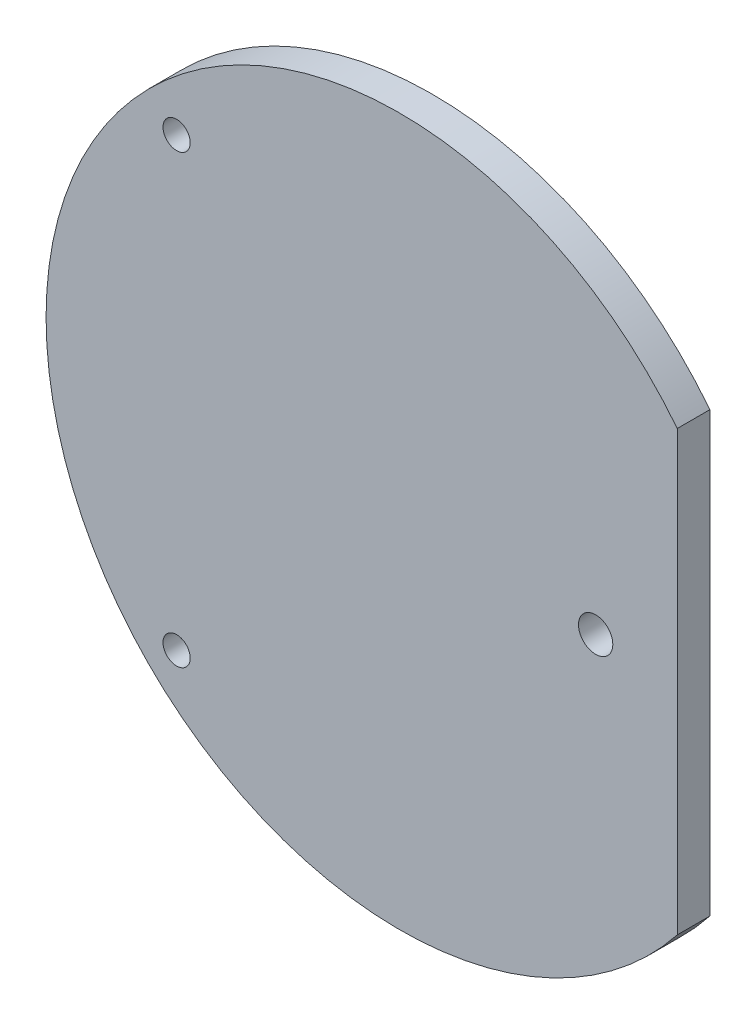
SolidWorks part; units mm, degrees
ref_plane "Спереди" through (0, 0, 0) normal (0, 0, 1) x (1, 0, 0)
ref_plane "Сверху" through (0, 0, 0) normal (0, 1, 0) x (1, 0, 0)
ref_plane "Справа" through (0, 0, 0) normal (1, 0, 0) x (0, 0, -1)
sketch "Эскиз1" plane through (0, 0, 0) normal (0, 0, 1) x (1, 0, 0)
  circle A0 centre (0, 0) radius 32.5
  dimension "D1" = 65
extrude "Бобышка-Вытянуть1" add sketch "Эскиз1" along normal blind 3
hole_wizard "Сверление под метчик M3x0.51" positions "Эскиз4" profile "Эскиз3" hole size "M3x0.5" standard "Ansi Metric"
sketch "Эскиз4" plane through (0, 0, 3) normal (0, 0, 1) x (1, 0, 0)
  line L1 (-36.4359, 0) -> (51.5308, 0) construction
  line L3 (0, 0) -> (-33.1888, 33.1888) construction
  circle A0 centre (0, 0) radius 29 construction
  circle A2 centre (-20.5061, 20.5061) radius 1.575
  circle A3 centre (-20.5061, -20.5061) radius 1.575
  point P31 (-20.5061, 20.5061)
  dimension "D1" = 58
  dimension "D2" = 3.15
  dimension "D3" = 45
sketch "Эскиз3" plane through (-20.5061, 20.5061, 3) normal (1, 0, 0) x (0, -1, 0)
  line L0 (0, 0) -> (0, 7.7511)
  line L1 (0, 7.7511) -> (1.25, 7)
  line L2 (1.25, 7) -> (1.25, 0)
  line L5 (1.25, 0) -> (0, 0)
  line L10 (0, 7.7511) -> (-1.25, 7) construction
  line L11 (0, -6.35) -> (0, 107.95) construction
  dimension "Диаметр отверстия" = 2.5
  dimension "Глубина отверстия" = 7
  dimension "Угол заточки сверла" = 118
pattern_circular "Круговой массив4" count 2 every 90 about axis through (0, 0, 3) along (0, 0, -1) of "Сверление под метчик M3x0.51" reverse direction yes
sketch "Эскиз5" plane through (0, 0, 0) normal (0, 0, -1) x (-1, 0, 0)
  line L0 (-25.5, -20.1494) -> (-25.5, 20.1494)
  arc A0 (-25.5, 20.1494) -> (-25.5, -20.1494) centre (0, 0) ccw
  point P5 (0, 0)
extrude "Вырез-Вытянуть2" cut sketch "Эскиз5" against normal blind 10
hole_wizard "Сверло под метчик  спиральное M31" positions "Эскиз6" profile "Эскиз7" hole size "M3x0.5" standard "Ansi Metric"
sketch "Эскиз6" plane through (0, 0, 3) normal (0, 0, 1) x (1, 0, 0)
  point P0 (18, 0)
  point P3 (14.9055, 0)
  dimension "D1" = 18
sketch "Эскиз7" plane through (18, 0, 3) normal (1, 0, 0) x (0, -1, 0)
  line L0 (0, 0) -> (0, 7.9464)
  line L1 (0, 7.9464) -> (1.575, 7)
  line L2 (1.575, 7) -> (1.575, 0)
  line L5 (1.575, 0) -> (0, 0)
  line L10 (0, 7.9464) -> (-1.575, 7) construction
  line L11 (0, -6.35) -> (0, 107.95) construction
  dimension "Диаметр отверстия" = 3.15
  dimension "Глубина отверстия" = 7
  dimension "Угол заточки сверла" = 118
